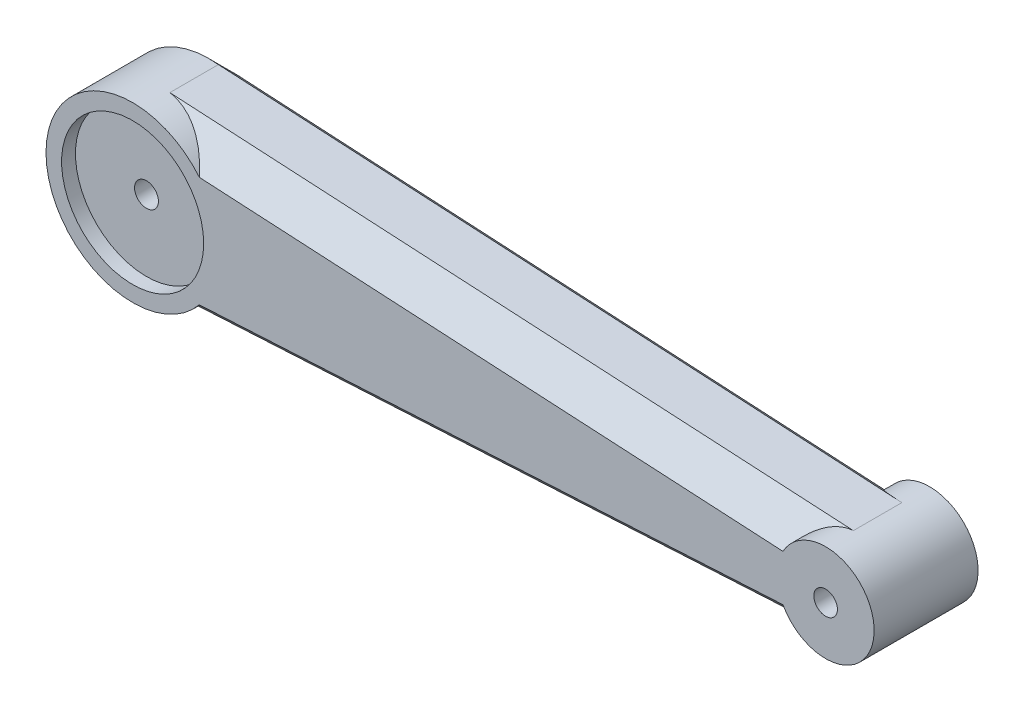
SolidWorks part; units mm, degrees
ref_plane "Front Plane" through (0, 0, 0) normal (0, 0, 1) x (1, 0, 0)
ref_plane "Top Plane" through (0, 0, 0) normal (0, 1, 0) x (1, 0, 0)
ref_plane "Right Plane" through (0, 0, 0) normal (1, 0, 0) x (0, 0, -1)
sketch "Sketch1" plane through (0, 0, 0) normal (0, 0, 1) x (1, 0, 0)
  line L0 (0, 0) -> (100, 0) construction
  line L1 (1.3709, 12.4246) -> (100, 7)
  line L2 (1.3709, -12.4246) -> (100, -7)
  arc A0 (1.3709, 12.4246) -> (1.3709, -12.4246) centre (0, 0) ccw
  arc A1 (100, -7) -> (100, 7) centre (100, 0) ccw
  dimension "D1" = 7
  dimension "D3" = 12.5
  dimension "D2" = 100
extrude "Boss-Extrude1" add sketch "Sketch1" along normal blind 15
chamfer "Chamfer1" distance 4 angle 45 3 edges at (50.6854, -9.7123, 0) (-12.5, 0, 0) (50.6854, 9.7123, 0)
sketch "Sketch2" plane through (0, 0, 15) normal (0, 0, 1) x (1, 0, 0)
  circle A0 centre (0, 0) radius 10.25
  dimension "D1" = 20.5
extrude "Cut-Extrude1" cut sketch "Sketch2" against normal blind 2
chamfer "Chamfer5" distance 4 angle 45 2 edges at (50.6854, -9.7123, 15) (50.6854, 9.7123, 15)
hole_wizard "CBORE for M5 Hex Head Cap Screw1" positions "Sketch3" profile "Sketch4" counterbore size "M5" standard "ANSI Metric" end condition through all
sketch "Sketch3" plane through (0, 0, 0) normal (0, 0, -1) x (-1, 0, 0)
  point P0 (0, 0)
sketch "Sketch4" plane through (0, 0, 0) normal (1, 0, 0) x (0, 1, 0)
  line L0 (0, 0) -> (0, 15)
  line L1 (0, 15) -> (1.725, 15)
  line L3 (1.725, 15) -> (1.725, 8)
  line L4 (4, 8) -> (1.725, 8)
  line L5 (4, 8) -> (4, 2.145)
  line L6 (4, 2.145) -> (6.145, 0)
  line L7 (6.145, 0) -> (0, 0)
  line L8 (-4, 2.145) -> (-6.145, 0) construction
  line L11 (0, -6.35) -> (0, 107.95) construction
  dimension "Thru Hole Dia." = 3.45
  dimension "Thru Hole Depth" = 15
  dimension "C'Bore Dia." = 8
  dimension "C'Bore Depth" = 8
  dimension "Near C'Sink Dia." = 12.29
  dimension "Near C'Sink Angle" = 90
hole_wizard "M3 Clearance Hole1" positions "Sketch5" profile "Sketch6" hole size "M3" standard "ANSI Metric" end condition through all
sketch "Sketch5" plane through (0, 0, 0) normal (0, 0, -1) x (-1, 0, 0)
  point P0 (-100, 0)
sketch "Sketch6" plane through (100, 0, 0) normal (1, 0, 0) x (0, 1, 0)
  line L0 (0, 0) -> (0, 15)
  line L1 (0, 15) -> (1.7, 15)
  line L2 (1.7, 15) -> (1.7, 0.025)
  line L3 (1.7, 0.025) -> (1.725, 0)
  line L5 (1.725, 0) -> (0, 0)
  line L6 (-1.7, 0.025) -> (-1.725, 0) construction
  line L11 (0, -6.35) -> (0, 107.95) construction
  dimension "Thru Hole Dia." = 3.4
  dimension "Thru Hole Depth" = 15
  dimension "Near C'Sink Dia." = 3.45
  dimension "Near C'Sink Angle" = 90
